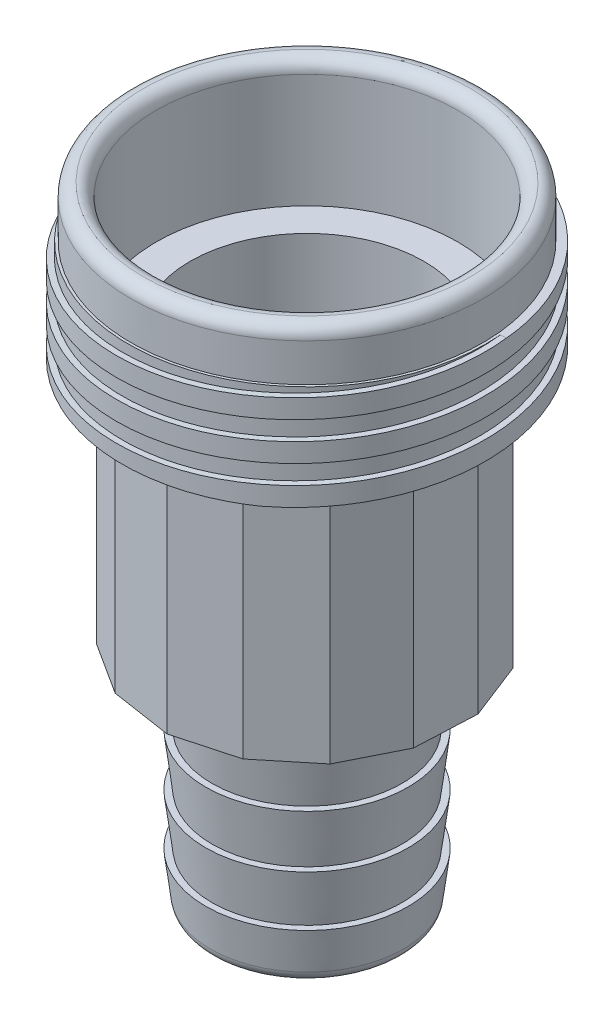
SolidWorks part; units mm, degrees
ref_plane "Front Plane" through (0, 0, 0) normal (0, 0, 1) x (1, 0, 0)
ref_plane "Top Plane" through (0, 0, 0) normal (0, 1, 0) x (1, 0, 0)
ref_plane "Right Plane" through (0, 0, 0) normal (1, 0, 0) x (0, 0, -1)
sketch "Sketch1" plane through (0, 0, 0) normal (0, 1, 0) x (1, 0, 0)
  line L0 (1.7742, 11.6223) -> (-3.1064, 11.3391)
  line L1 (5.396, -10.4455) -> (9.1781, -7.3477)
  line L2 (9.1781, -7.3477) -> (11.3731, -2.9794)
  line L3 (11.3731, -2.9794) -> (11.6017, 1.9041)
  line L4 (11.6017, 1.9041) -> (9.8242, 6.4583)
  line L5 (9.8242, 6.4583) -> (6.3481, 9.8958)
  line L6 (6.3481, 9.8958) -> (1.7742, 11.6223)
  line L7 (-3.1064, 11.3391) -> (-7.4498, 9.0953)
  line L8 (-7.4498, 9.0953) -> (-10.5052, 5.2789)
  line L9 (-10.5052, 5.2789) -> (-11.7441, 0.5497)
  line L10 (-11.7441, 0.5497) -> (-10.9523, -4.2746)
  line L11 (-10.9523, -4.2746) -> (-8.2668, -8.3597)
  line L12 (-8.2668, -8.3597) -> (-4.1519, -10.9994)
  line L13 (-4.1519, -10.9994) -> (0.6809, -11.7372)
  line L14 (0.6809, -11.7372) -> (5.396, -10.4455)
  circle A0 centre (0, 0) radius 11.5 construction
  dimension "D1" = 23
extrude "Boss-Extrude1" add sketch "Sketch1" along normal blind 20
sketch "Sketch3" plane through (0, 0, 0) normal (1, 0, 0) x (0, 0, -1)
  line L0 (0, 0) -> (0, -33.6441) construction
  line L1 (-7.5, -18) -> (0, -18)
  line L2 (-7.3477, 0) -> (-2.9794, 0) construction
  line L3 (-7.5, -18) -> (-8, -14)
  line L4 (-8, -1.699) -> (-8, 0.3245)
  line L5 (-8, -14) -> (-7.5, -14)
  line L6 (-7.5, -14) -> (-8, -10)
  line L7 (-8, -10) -> (-7.5, -10)
  line L8 (-7.5, -10) -> (-8, -5.8495)
  line L9 (-8, -5.8495) -> (-7.5, -5.8495)
  line L10 (-7.5, -5.8495) -> (-8, -1.699)
  line L11 (-8, 0.3245) -> (0, 0.3245)
  line L12 (0, 0.3245) -> (0, -18)
  dimension "D1" = 18
  dimension "D2" = 7.5
  dimension "D3" = 8
  dimension "D4" = 4
  dimension "D5" = 4
revolve "Revolve1" add sketch "Sketch3" angle 360 about L0
sketch "Sketch5" plane through (0, 0, 0) normal (1, 0, 0) x (0, 0, -1)
  line L0 (0, 0) -> (0, 40.5815) construction
  line L1 (0, 19.2097) -> (-14.1, 19.2097)
  line L2 (-14.1, 19.2097) -> (-14.1, 32.2097)
  line L3 (-14.1, 32.2097) -> (-14, 32.2097)
  line L4 (-14, 32.2097) -> (-14, 36.2097)
  line L5 (-14, 36.2097) -> (0, 36.2097)
  line L6 (0, 36.2097) -> (0, 19.2097)
  dimension "D1" = 28.2
  dimension "D2" = 13
  dimension "D3" = 4
  dimension "D4" = 28
revolve "Revolve2" add sketch "Sketch5" angle 360 about L0
sketch "Sketch7" plane through (0, 19.2097, 0) normal (0, -1, 0) x (1, 0, 0)
  circle A0 centre (0, 0) radius 14.6
ref_plane "Plane1" through (0, 14.2097, 0) normal (0, -1, 0) x (-1, 0, 0)
sketch "Sketch12" plane through (0, 0, 0) normal (1, 0, 0) x (0, 0, -1)
  line L0 (-14.5605, 20.7097) -> (-14.0605, 20.7097)
  line L1 (-14.0605, 20.7097) -> (-14.0605, 19.2097)
  line L2 (-14.0605, 19.2097) -> (-14.5605, 19.2097)
  line L3 (-14.5605, 19.2097) -> (-14.5605, 20.7097)
  line L5 (-14.0605, 19.2097) -> (-14.1, 20.9686) construction
  line L6 (-14.1, 19.2097) -> (14.1, 19.2097) construction
  point P8 (-14.0347, 19.2097)
  point P10 (-14.1, 20.9686)
  dimension "D1" = 0.5
  dimension "D2" = 1.5
sketch "Sketch13" plane through (0, 14.2097, 0) normal (0, -1, 0) x (-1, 0, 0)
  circle A0 centre (0, 0) radius 14.1
  dimension "D1" = 28.2
curve "Helix/Spiral3" pitch 3 height 24 radius 14.1 centre (0, 14.2097, 0) axis (0, 1, 0) start towards (0.7071, 0, 0.7071)
sweep "Sweep1" add profiles "Sketch12" path "Helix/Spiral3"
sketch "Sketch14" plane through (0, 0, 0) normal (1, 0, 0) x (0, 0, -1)
  line L0 (0, 0) -> (0, 51.2251) construction
  line L1 (-15.5667, 13.0738) -> (-11.939, 13.0738)
  line L2 (-11.939, 13.0738) -> (-11.939, 19.5)
  line L3 (-11.939, 19.5) -> (-15.5667, 19.5)
  line L4 (-15.5667, 19.5) -> (-15.5667, 13.0738)
  line L5 (0, 31.5) -> (-13.9, 31.5)
  line L6 (-13.9, 31.5) -> (-13.9, 27.5)
  line L7 (-13.9, 27.5) -> (-25.4412, 27.5)
  line L8 (-25.4412, 27.5) -> (-25.4412, 44.7395)
  line L9 (-25.4412, 44.7395) -> (0, 44.7395)
  line L10 (0, 44.7395) -> (0, 31.5)
  line L11 (-10.4455, 0) -> (-7.3477, 0) construction
  point P15 (-19.6706, 27.5)
  dimension "D1" = 19.5
  dimension "D2" = 8
  dimension "D3" = 27.8
  dimension "D4" = 4
revolve "Cut-Revolve1" cut sketch "Sketch14" angle 360 about L0
sketch "Sketch15" plane through (0, 0, 0) normal (1, 0, 0) x (0, 0, -1)
  line L0 (0, -27.9176) -> (0, 51.8377) construction
  line L1 (-11.9, 44.3952) -> (-11.9, 21.5)
  line L2 (-11.9, 21.5) -> (-9.2372, 21.5)
  line L3 (-9.2372, 21.5) -> (-9.2372, 2)
  line L6 (0, -27.9176) -> (0, 44.3952)
  line L7 (0, 44.3952) -> (-11.9, 44.3952)
  line L8 (-13.9, 31.5) -> (-13.9, 27.5) construction
  line L9 (-14.5605, 19.5) -> (11.9655, 19.5) construction
  line L10 (-9.2372, 2) -> (-6, 2)
  line L11 (-6, 2) -> (-6, -27.9176)
  line L12 (-6, -27.9176) -> (0, -27.9176)
  line L13 (-7.3477, 0) -> (-2.9794, 0) construction
  point P5 (0.2119, -26.5643)
  dimension "D1" = 2
  dimension "D2" = 2
  dimension "D3" = 2.5
  dimension "D4" = 2
  dimension "D5" = 1.5
revolve "Cut-Revolve2" cut sketch "Sketch15" angle 360 about L0
fillet "Fillet1" radius 1 3 edges at (0, 31.5, 11.9) (0, 31.5, -13.9) (0, -18, 7.5)
